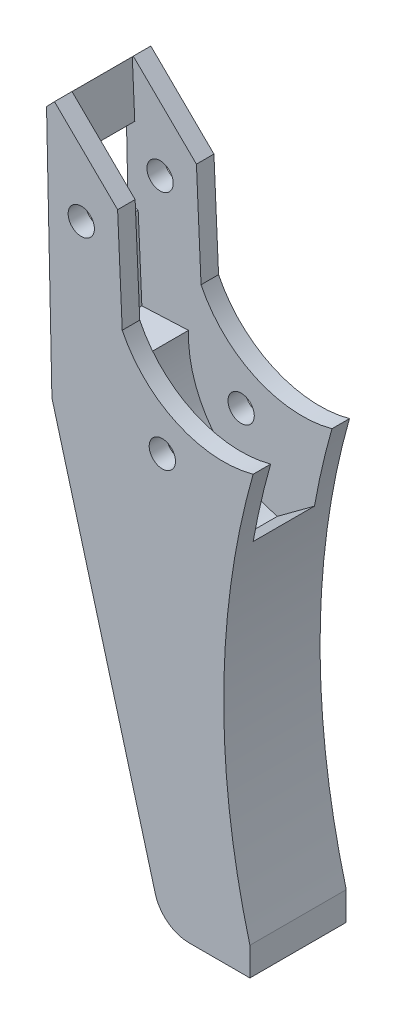
SolidWorks part; units mm, degrees
ref_plane "Front Plane" through (0, 0, 0) normal (0, 0, 1) x (1, 0, 0)
ref_plane "Top Plane" through (0, 0, 0) normal (0, 1, 0) x (1, 0, 0)
ref_plane "Right Plane" through (0, 0, 0) normal (1, 0, 0) x (0, 0, -1)
sketch "Sketch2" plane through (0, 0, 0) normal (0, 0, 1) x (1, 0, 0)
  line L0 (-63.9671, -130.8596) -> (-76.6671, -130.8596)
  line L1 (-76.6671, -130.8596) -> (-92.6781, -72.3642)
  line L2 (-92.6781, -72.3642) -> (-93.5094, -33.7907)
  line L3 (-93.5094, -33.7907) -> (-83.1529, -43.9607)
  line L4 (-83.1529, -43.9607) -> (-82.4817, -58.7689)
  line L5 (-63.9671, -130.8596) -> (-63.9671, -126.7453)
  arc A0 (-63.9671, -126.7453) -> (-63.5, -67.3596) centre (43.7734, -97.898) cw
  arc A1 (-63.5, -67.3596) -> (-82.4817, -58.7689) centre (-67.7975, -51.5892) cw
  circle A2 centre (-88.4241, -48.0538) radius 1.905
  circle A3 centre (-76.6671, -71.3707) radius 1.905
  dimension "D3" = 3.81
  dimension "D4" = 3.81
  dimension "D1" = 12.7
  dimension "D2" = 63.5
  dimension "D5" = 41.275
  dimension "D6" = 13.1671
  dimension "D7" = 5.2711
extrude "Boss-Extrude1" add sketch "Sketch2" against normal blind 13.97
sketch "Sketch7" plane through (-84.9711, -3.8518, 0) normal (0.999, 0.0453, 0) x (0, 0, -1)
  line L0 (13.97, -54.9735) -> (13.97, -40.1501) construction
  line L1 (11.43, -47.7841) -> (2.54, -47.7841)
  line L2 (11.43, -47.7841) -> (11.43, -61.5208)
  line L3 (11.43, -61.5208) -> (2.54, -61.5208)
  line L4 (2.54, -47.7841) -> (2.54, -61.5208)
  line L5 (0, -54.9735) -> (0, -40.1501) construction
  dimension "D1" = 2.54
  dimension "D2" = 2.54
extrude "Cut-Extrude1" cut sketch "Sketch7" against normal blind 8.89
sketch "Sketch8" plane through (2.1639, -47.7351, 0) normal (0.0453, -0.999, 0) x (0.999, 0.0453, 0)
  line L0 (-93.9484, -2.54) -> (-85.0584, -2.54) construction
  line L1 (-93.9484, -2.54) -> (-93.9484, -11.43) construction
  line L2 (-93.9484, -11.43) -> (-85.0584, -11.43) construction
  line L3 (-77.9583, -11.43) -> (-77.9583, -2.54) construction
  line L4 (-93.9484, -2.54) -> (-77.9583, -2.54)
  line L5 (-93.9484, -2.54) -> (-93.9484, -11.43)
  line L6 (-93.9484, -11.43) -> (-77.9583, -11.43)
  line L7 (-77.9583, -11.43) -> (-77.9583, -2.54)
extrude "Cut-Extrude2" cut sketch "Sketch8" against normal blind 38.354
sketch "Sketch9" plane through (0, 0, 0) normal (0, 0, 1) x (1, 0, 0)
  line L0 (-82.4817, -58.7689) -> (-84.3011, -65.398)
  line L1 (-71.4197, -82.3236) -> (-53.044, -68.7593)
  line L2 (-53.044, -68.7593) -> (-82.4817, -58.7689)
  arc A0 (-84.3011, -65.398) -> (-71.4197, -82.3236) centre (-67.466, -65.95) ccw
extrude "Cut-Extrude4" cut sketch "Sketch9" along direction (0, 0, 1) on the side against the normal blind 8.89 from offset 2.54 contours L2 L0 A0 L1 offset against normal yes
fillet "Fillet1" radius 5.08 1 edges at (-76.6671, -130.8596, -6.985)
chamfer "Chamfer1" distance 2.38 angle 45 1 edges at (-93.5094, -33.7907, -6.985) first distance on face at (-93.0938, -53.0775, -6.985)
sketch "Sketch10" plane through (0, 0, -11.43) normal (0, 0, 1) x (1, 0, 0)
  spline S0 degree 3 poles (-87.675, -48.2164) (-91.6332, -40.275) (-96.6951, -48.735) (-91.0175, -56.7217) (-87.675, -48.2164) (-91.6332, -40.275) (-96.6951, -48.735) knots -0.732616 -0.486365 -0.227047 0 0.267384 0.513635 0.772953 1 1.267384 1.513635 1.772953 only from (-91.5864, -42.9893) to (-91.5864, -42.9893)
  point P2 (-91.4473, -53.9549)
  point P4 (-91.5864, -42.9893)
extrude "Cut-Extrude5" cut sketch "Sketch10" along normal up to surface (8.89 mm away) up to face at (-81.2679, -59.7382, -2.54)
